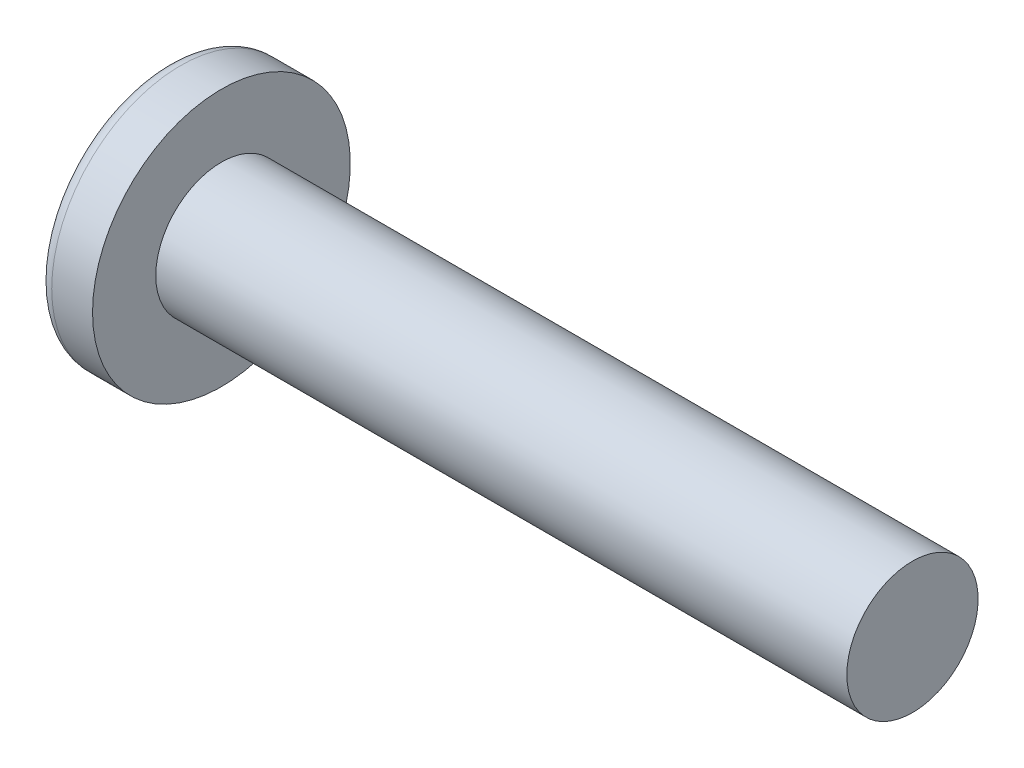
SolidWorks part; units mm, degrees
ref_plane "Plane1" through (0, 0, 0) normal (0, 0, 1) x (1, 0, 0)
ref_plane "Plane2" through (0, 0, 0) normal (0, 1, 0) x (1, 0, 0)
ref_plane "Plane3" through (0, 0, 0) normal (1, 0, 0) x (0, 0, -1)
sketch "BodySke" plane through (0, 0, 0) normal (0, 0, 1) x (1, 0, 0)
  line L0 (3.3782, 2.413) -> (3.3782, 4.7371)
  line L1 (3.9078, 6.35) -> (3.9078, -3.175) construction
  line L2 (-25.4, 0) -> (127, 0) construction
  line L3 (28.7782, 0) -> (0, 0)
  line L4 (3.3782, 2.413) -> (28.7782, 2.413)
  line L5 (28.7782, 2.413) -> (28.7782, 0)
  line L6 (1.8777, 4.7371) -> (3.3782, 4.7371)
  line L7 (3.3782, -2.413) -> (28.7782, -2.413) construction
  line L8 (3.3782, 6.35) -> (3.3782, -3.175) construction
  arc A0 (1.4662, 4.5269) -> (0, 0) centre (7.7216, 0) ccw
  arc A2 (1.4662, 4.5269) -> (1.8777, 4.7371) centre (1.8777, 4.2291) cw
  dimension "Head_fillet_rad" = 0.508
  dimension "Head_crown_rad" = 7.7216
  dimension "Head_ht" = 3.3782
  dimension "Diameter" = 4.826
  dimension "Length" = 25.4
  dimension "Head_dia" = 9.4742
  dimension "Advance" = 1.0592
  dimension "Thread_nom" = 25.4
revolve "Base-Revolve" add sketch "BodySke" angle 360 about L2
cosmetic thread "ThreadCosmetic" [suppressed] parameters "Thread_length"=24.3408, "Thread_minor"=3.5662
sketch "Sketch3" plane through (0, 0, 0) normal (1, 0, 0) x (0, 0, -1)
  line L0 (0.5842, -3.048) -> (-0.5842, -3.048)
  line L1 (0.5842, -3.048) -> (0.5842, 3.048)
  line L2 (-0.5842, 3.048) -> (0.5842, 3.048)
  line L3 (-0.5842, 3.048) -> (-0.5842, -3.048)
  dimension "D1" = 3.048
  dimension "Cross_dia" = 6.096
  dimension "D2" = 0.5842
  dimension "Cross_width" = 1.1684
ref_plane "Plane4" through (3.4798, 0, 0) normal (1, 0, 0) x (0, 0, -1)
sketch "Sketch4" plane through (3.4798, 0, 0) normal (1, 0, 0) x (0, 0, -1)
  line L0 (0.2921, -0.2921) -> (-0.2921, -0.2921)
  line L1 (0.2921, -0.2921) -> (0.2921, 0.2921)
  line L2 (-0.2921, 0.2921) -> (0.2921, 0.2921)
  line L3 (-0.2921, 0.2921) -> (-0.2921, -0.2921)
  dimension "D1" = 0.5842
  dimension "D2" = 0.5842
  dimension "D3" = 0.2921
  dimension "D4" = 0.2921
loft "Cut-Loft1" cut profiles "Sketch3", "Sketch4"
pattern_circular "CirPattern1" count 2 every 90 about axis through (-25.4, 0, 0) along (1, 0, 0) of "Cut-Loft1"
sketch "ThdSchSke" plane through (0, 0, 0) normal (0, 0, 1) x (1, 0, 0)
  line L0 (4.4374, -1.7831) -> (3.9963, -2.413)
  line L1 (4.4374, -1.7831) -> (4.8785, -2.413)
  line L2 (4.8785, -2.413) -> (4.8785, -3.0162)
  line L3 (-3.175, 0) -> (5.1513, 0) construction
  line L5 (4.8785, -3.0162) -> (3.9963, -3.0162)
  line L6 (3.9963, -3.0162) -> (3.9963, -2.413)
  dimension "Thread_minor" = 3.5662
  dimension "Diameter" = 4.826
  dimension "Start" = 4.4374
  dimension "SideAngle" = 55
  dimension "VeeAngle" = 70
  dimension "Overcut" = 6.0325
revolve "ThreadSchematic" [suppressed] cut sketch "ThdSchSke" angle 360 about L3
pattern_linear "ThdSchPat" [suppressed]
equation "\"D1@Sketch3\" = \"Cross_dia@Sketch3\" / 2"
equation "\"D2@Sketch3\" = \"Cross_width@Sketch3\" / 2"
equation "\"D1@Sketch4\" = \"Cross_width@Sketch3\" *.5"
equation "\"D2@Sketch4\" = \"D1@Sketch4\""
equation "\"D3@Sketch4\" = \"D1@Sketch4\" / 2"
equation "\"D4@Sketch4\" = \"D2@Sketch4\" / 2"
equation "\"Thread_length@ThreadCosmetic\" = ((sgn( (\"Length@BodySke\" - \"Advance@BodySke\" ) - \"Thread_nom@BodySke\" )-1)*( (\"Length@BodySke\" - \"Advance@BodySke\" ) - \"Thread_nom@BodySke\" ))/-2+ \"Thread_nom@BodySke\""
equation "\"Thread_minor@ThdSchSke\" = \"Thread_minor@ThreadCosmetic\""
equation "\"Diameter@ThdSchSke\" = \"Diameter@BodySke\""
equation "\"Overcut@ThdSchSke\" = \"Diameter@BodySke\" * 1.25"
equation "\"Start@ThdSchSke\" = \"Head_ht@BodySke\" + \"Length@BodySke\" - \"Thread_length@ThreadCosmetic\"  '---Non-countersunk---"
equation "\"Num_threads@ThdSchPat\" = int( \"Thread_length@ThreadCosmetic\" / \"Advance@BodySke\" + 0.999 )  + 1"
equation "\"Advance@ThdSchPat\" = \"Thread_length@ThreadCosmetic\" /  (\"Num_threads@ThdSchPat\" - 1) 'relax it"
